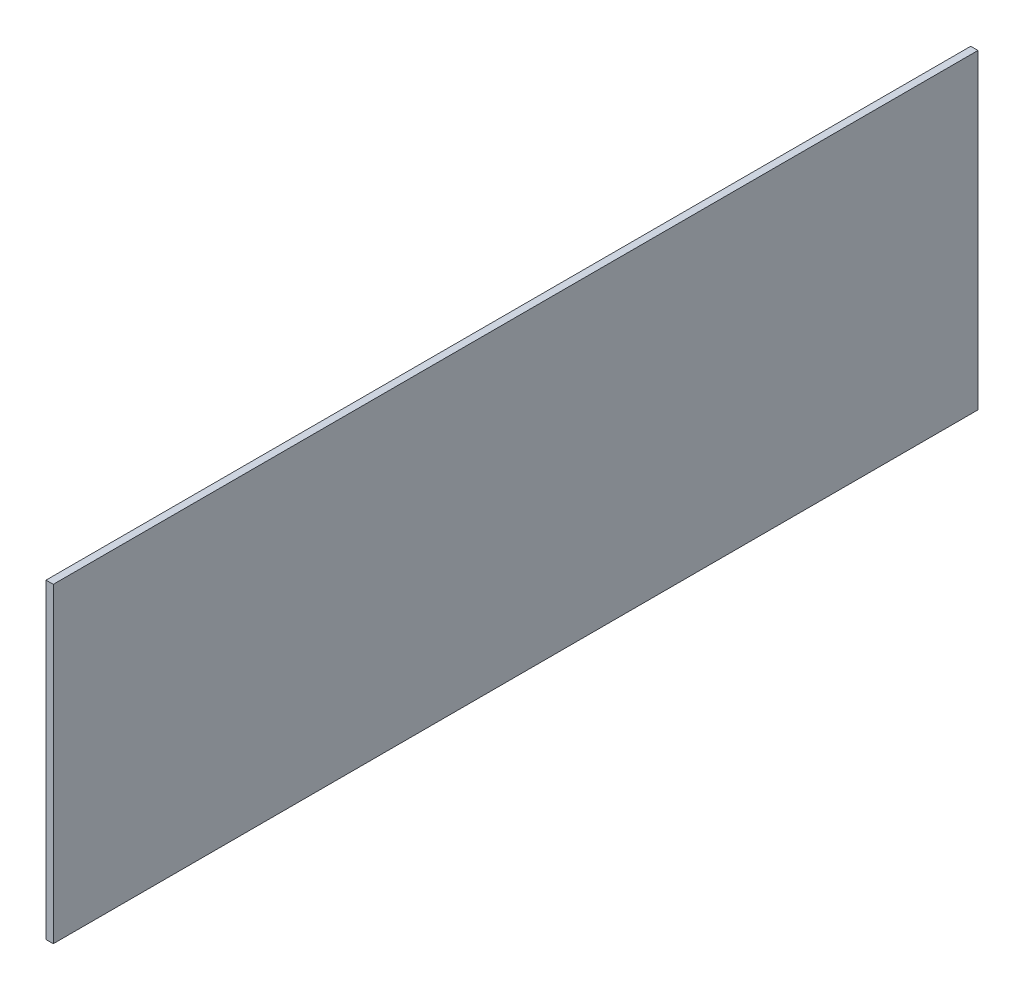
SolidWorks part; units mm, degrees
material "6061-T6 (SS)"
ref_plane "Front" through (0, 0, 0) normal (0, 0, 1) x (1, 0, 0)
ref_plane "Top" through (0, 0, 0) normal (0, 1, 0) x (1, 0, 0)
ref_plane "Right" through (0, 0, 0) normal (1, 0, 0) x (0, 0, -1)
sketch "Sketch1" plane through (0, 0, 0) normal (0, 0, 1) x (1, 0, 0)
  line L0 (-247, 3) -> (247, 3)
  line L1 (-250, 0) -> (250, 0)
  line L2 (-250, 0) -> (-250, 500)
  line L3 (-250, 500) -> (250, 500)
  line L4 (250, 0) -> (250, 500)
  line L5 (247, 3) -> (247, 497)
  line L6 (-247, 497) -> (247, 497)
  line L7 (-247, 3) -> (-247, 497)
  line L8 (-142.0145, 497) -> (-142.0145, 368.6667) construction
  line L9 (-247, 368.6667) -> (247, 368.6667)
  line L10 (-247, 368.6667) -> (-247, 365.6667)
  line L11 (-247, 365.6667) -> (247, 365.6667)
  line L12 (247, 368.6667) -> (247, 365.6667)
  line L13 (-247, 237.3333) -> (247, 237.3333)
  line L14 (-247, 237.3333) -> (-247, 234.3333)
  line L15 (-247, 234.3333) -> (247, 234.3333)
  line L16 (247, 237.3333) -> (247, 234.3333)
  line L17 (-247, 106) -> (247, 106)
  line L18 (-247, 106) -> (-247, 103)
  line L19 (-247, 103) -> (247, 103)
  line L20 (247, 106) -> (247, 103)
  line L21 (-142.0145, 365.6667) -> (-142.0145, 237.3333) construction
  line L22 (-142.0145, 234.3333) -> (-142.0145, 106) construction
  line L23 (-247, 432.8333) -> (-84.3333, 432.8333) construction
  line L24 (-84.3333, 497) -> (-81.3333, 497)
  line L25 (-84.3333, 497) -> (-84.3333, 368.6667)
  line L26 (-84.3333, 368.6667) -> (-81.3333, 368.6667)
  line L27 (-81.3333, 497) -> (-81.3333, 368.6667)
  line L28 (81.3333, 497) -> (84.3333, 497)
  line L29 (81.3333, 497) -> (81.3333, 368.6667)
  line L30 (81.3333, 368.6667) -> (84.3333, 368.6667)
  line L31 (84.3333, 497) -> (84.3333, 368.6667)
  line L32 (-81.3333, 432.8333) -> (81.3333, 432.8333) construction
  line L33 (84.3333, 432.8333) -> (247, 432.8333) construction
  point P41 (0, 0)
  point P42 (0, 0)
  point P43 (247, 432.8333)
  dimension "D1" = 500
  dimension "D2" = 3
  dimension "D3" = 3
  dimension "D4" = 100
  dimension "D5" = 3
extrude "Boss-Extrude1" add sketch "Sketch1" along normal blind 381.25 contours L27 L6 L25 L9 region at (-82.8333, 432.8333, 0)
